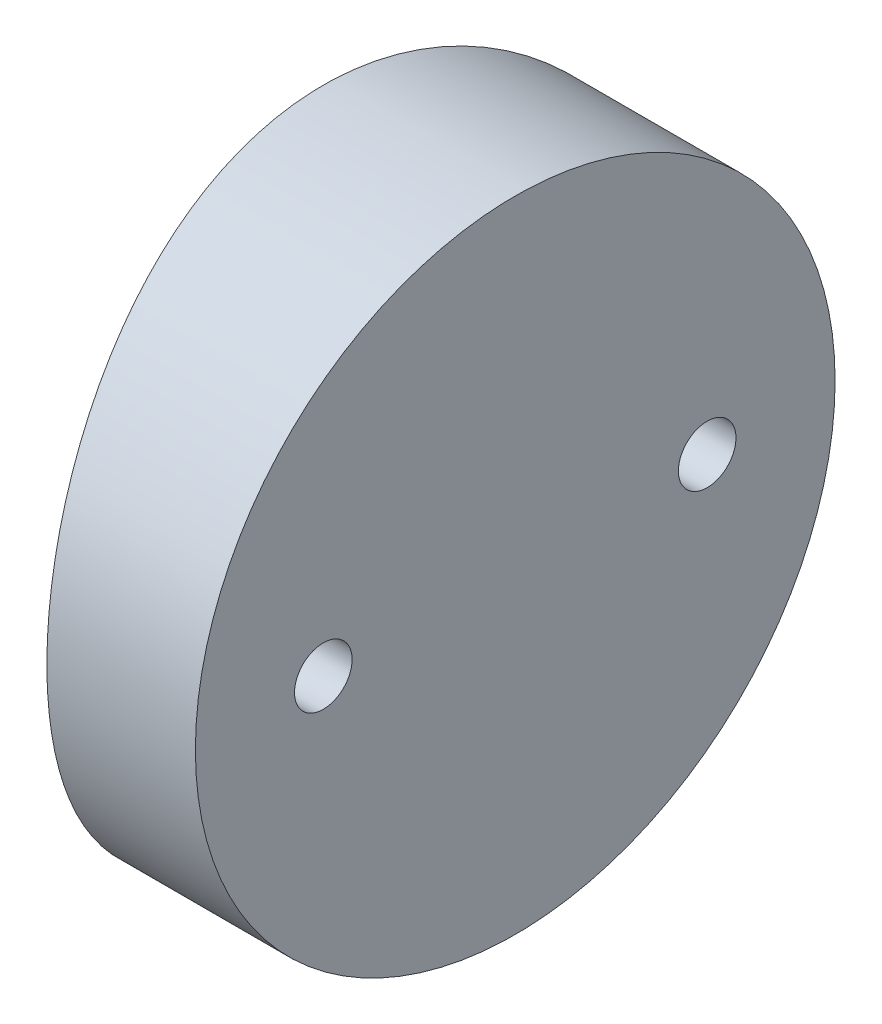
SolidWorks part; units mm, degrees
ref_plane "Plano frontal" through (0, 0, 0) normal (0, 0, 1) x (1, 0, 0)
ref_plane "Plano superior" through (0, 0, 0) normal (0, 1, 0) x (1, 0, 0)
ref_plane "Plano direito" through (0, 0, 0) normal (1, 0, 0) x (0, 0, -1)
sketch "Sketch1" plane through (0, 0, 0) normal (1, 0, 0) x (0, 0, -1)
  circle A0 centre (0, 0) radius 20
  dimension "D1" = 40
extrude "Bloco" add sketch "Sketch1" along normal blind 12
hole_wizard "Furo de Fixação - Parafuso M3" positions "Sketch5" profile "Sketch6" countersink size "M3" standard "ANSI Metric" end condition up to next
sketch "Sketch5" plane through (0, 0, 0) normal (-1, 0, 0) x (0, 0, 1)
  point P10 (-12, 0)
  point P12 (12, 0)
  dimension "D1" = 24
  dimension "D2" = 12
sketch "Sketch6" plane through (0, 0, -12) normal (0, 1, 0) x (0, 0, 1)
  line L0 (0, 0) -> (0, 12)
  line L1 (0, 12) -> (1.8, 12)
  line L2 (1.8, 12) -> (1.8, 1.56)
  line L3 (1.8, 1.56) -> (3.36, 0)
  line L5 (3.36, 0) -> (0, 0)
  line L6 (-1.8, 1.56) -> (-3.36, 0) construction
  line L11 (0, -6.35) -> (0, 107.95) construction
  dimension "Thru Hole Dia." = 3.6
  dimension "Thru Hole Depth" = 12
  dimension "Near C'Sink Dia." = 6.72
  dimension "Near C'Sink Angle" = 90
sketch "Sketch7" plane through (0, 0, 0) normal (0, 1, 0) x (1, 0, 0)
  circle A0 centre (75, 0) radius 75
  circle A1 centre (75, 0) radius 75
  circle A2 centre (75, 0) radius 100
  dimension "D2" = 200
  dimension "D1" = 75
extrude "Corte - Arredondamento" cut sketch "Sketch7" against normal through all both and the other way through all contours A2 A0 region at (-22.1716, 0, 0)
